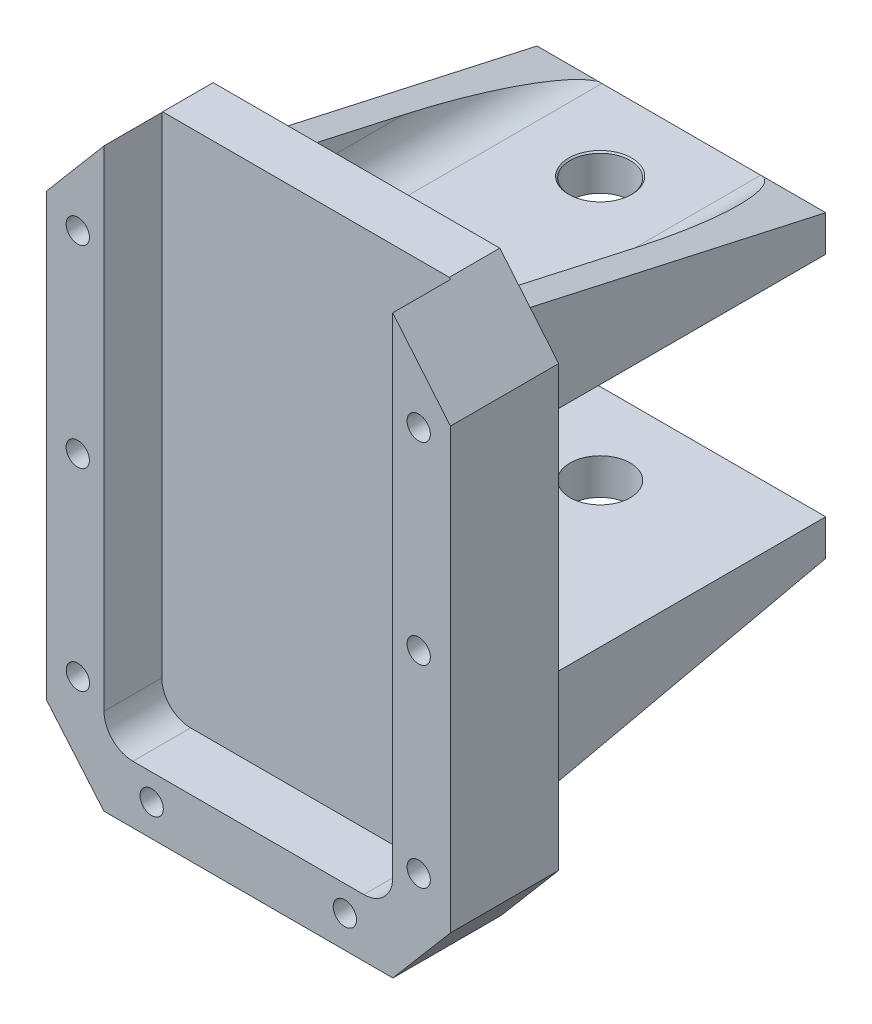
SolidWorks part; units mm, degrees
material "PET"
ref_plane "Front Plane" through (0, 0, 0) normal (0, 0, 1) x (1, 0, 0)
ref_plane "Top Plane" through (0, 0, 0) normal (0, 1, 0) x (1, 0, 0)
ref_plane "Right Plane" through (0, 0, 0) normal (1, 0, 0) x (0, 0, -1)
sketch "Sketch1" plane through (0, 0, 0) normal (0, 0, 1) x (1, 0, 0)
  line L1 (0, 0) -> (-35.56, 0)
  line L2 (0, 0) -> (0, 50.8)
  line L3 (0, 50.8) -> (-35.56, 50.8)
  line L4 (-35.56, 0) -> (-35.56, 50.8)
  dimension "D1" = 50.8
  dimension "D2" = 35.56
extrude "Boss-Extrude1" add sketch "Sketch1" along normal blind 9.525
sketch "Sketch2" plane through (0, 0, 9.525) normal (0, 0, 1) x (1, 0, 0)
  line L0 (0, 50.8) -> (-35.56, 50.8) construction
  line L1 (-30.48, 50.8) -> (-5.08, 50.8)
  line L2 (-30.48, 50.8) -> (-30.48, 5.08)
  line L3 (-30.48, 5.08) -> (-5.08, 5.08)
  line L4 (-5.08, 50.8) -> (-5.08, 5.08)
  line L5 (-35.56, 0) -> (0, 0) construction
  line L6 (-17.78, 0) -> (-17.78, 5.08) construction
  dimension "D1" = 45.72
  dimension "D2" = 25.4
extrude "Cut-Extrude2" cut sketch "Sketch2" against normal blind 5.08
hole_wizard "Tap Drill for M2.5x0.45 Tap1" positions "Sketch6" profile "Sketch5" hole size "M2.5x0.45" standard "ANSI Metric" end condition through all
sketch "Sketch6" plane through (0, 0, 0) normal (0, 0, -1) x (-1, 0, 0)
  point P0 (2.7924, 43.0871)
  point P2 (2.7924, 26.093)
  point P4 (2.7924, 9.1052)
  point P6 (9.2907, 2.8227)
  point P8 (26.2924, 2.7871)
  point P10 (32.78, 9.1052)
  point P12 (32.7924, 26.0871)
  point P14 (32.7924, 43.0871)
sketch "Sketch5" plane through (-2.7924, 43.0871, 0) normal (1, 0, 0) x (0, 1, 0)
  line L0 (0, 0) -> (0, 9.525)
  line L1 (0, 9.525) -> (1.025, 9.525)
  line L2 (1.025, 9.525) -> (1.025, 0)
  line L5 (1.025, 0) -> (0, 0)
  line L11 (0, -6.35) -> (0, 107.95) construction
  dimension "Thru Hole Dia." = 2.05
  dimension "Thru Hole Depth" = 9.525
sketch "Sketch13" plane through (0, 0, 0) normal (0, 0, -1) x (-1, 0, 0)
  line L0 (35.56, 0) -> (0, 0) construction
  line L1 (30.48, 39.265) -> (5.08, 39.265)
  line L2 (30.48, 39.265) -> (30.48, 36.09)
  line L3 (30.48, 36.09) -> (5.08, 36.09)
  line L4 (5.08, 39.265) -> (5.08, 36.09)
  line L5 (30.48, 39.265) -> (5.08, 36.09) construction
  line L6 (30.48, 36.09) -> (5.08, 39.265) construction
  line L7 (30.48, 16.09) -> (5.08, 16.09)
  line L8 (30.48, 16.09) -> (30.48, 12.915)
  line L9 (30.48, 12.915) -> (5.08, 12.915)
  line L10 (5.08, 16.09) -> (5.08, 12.915)
  line L11 (30.48, 16.09) -> (5.08, 12.915) construction
  line L12 (30.48, 12.915) -> (5.08, 16.09) construction
  line L13 (17.78, 16.09) -> (17.78, 36.09) construction
  line L15 (0, 50.8) -> (35.56, 50.8) construction
  point P0 (17.78, 37.6775)
  point P5 (17.78, 14.5025)
  point P12 (17.78, 0)
  point P15 (17.78, 26.09)
  dimension "D1" = 3.175
  dimension "D2" = 3.175
  dimension "D3" = 25.4
  dimension "D4" = 20
  dimension "D5" = 24.71
extrude "Boss-Extrude2" add sketch "Sketch13" along normal blind 28.575
sketch "Sketch8" plane through (0, 0, 9.525) normal (0, 0, 1) x (1, 0, 0)
  line L0 (-5.179, 50.8) -> (0, 44.5915)
  line L1 (-5.08, 50.8) -> (-30.48, 50.8) construction
  line L2 (0, 0) -> (0, 50.8) construction
  line L3 (0.0027, 44.5883) -> (-5.0973, 50.5883) construction
  line L4 (0, 44.5915) -> (0, 50.8)
  line L5 (0, 50.8) -> (-5.179, 50.8)
  line L6 (-35.56, 44.7066) -> (-35.56, 50.8)
  line L7 (-35.56, 50.8) -> (-35.56, 0) construction
  line L8 (-35.56, 50.8) -> (-30.4026, 50.8)
  line L9 (-30.4026, 50.8) -> (-35.56, 44.7066)
  line L10 (-35.56, 5.97) -> (-35.56, 0)
  line L11 (-35.56, 0) -> (-30.4926, 0)
  line L12 (-35.56, 0) -> (0, 0) construction
  line L13 (-30.4926, 0) -> (-35.56, 5.97)
  line L14 (-5.0926, -0.0313) -> (0, 0)
  line L15 (0, 0) -> (0, 5.97)
  line L16 (0, 5.97) -> (-5.0926, -0.0313)
extrude "Cut-Extrude3" cut sketch "Sketch8" against normal through all
ref_plane "Plane6" through (-23.56, 0, 0) normal (-1, 0, 0) x (0, 0, 1)
fillet "Fillet1" radius 2.54 2 edges at (-5.08, 5.08, 6.985) (-30.48, 5.08, 6.985)
sketch "Sketch10" plane through (-43.87, 39.265, 0) normal (0, -1, 0) x (0, 0, -1)
  line L2 (14.2875, 13.39) -> (14.2875, 38.79) construction
  line L3 (0, 38.79) -> (0, 13.39) construction
  line L4 (14.2875, 26.09) -> (0, 26.09) construction
  line L6 (28.575, 13.39) -> (0, 13.39) construction
  line L7 (28.575, 38.79) -> (0, 38.79) construction
  line L8 (14.2875, 26.09) -> (28.575, 26.09) construction
  line L9 (28.575, 38.79) -> (28.575, 13.39) construction
  circle A0 centre (21.4312, 26.09) radius 3.175
  circle A1 centre (7.1438, 26.09) radius 3.175
  point P10 (23.8125, 26.09)
  dimension "D1" = 6.35
hole_wizard "M5 Clearance Hole1" positions "3DSketch1" profile "Sketch11" hole size "M5" standard "ANSI Metric" end condition through all
sketch3d "3DSketch1"
  point P0 (-17.78, 39.265, -7.1438)
  point P3 (-17.78, 39.265, -21.4312)
sketch "Sketch11" plane through (-17.78, 39.265, -7.1438) normal (1, 0, 0) x (0, 0, 1)
  line L0 (0, 0) -> (0, 39.265)
  line L1 (0, 39.265) -> (2.65, 39.265)
  line L2 (2.65, 39.265) -> (2.65, 0.125)
  line L3 (2.65, 0.125) -> (2.775, 0)
  line L5 (2.775, 0) -> (0, 0)
  line L6 (-2.65, 0.125) -> (-2.775, 0) construction
  line L11 (0, -6.35) -> (0, 107.95) construction
  dimension "Thru Hole Dia." = 5.3
  dimension "Thru Hole Depth" = 39.265
  dimension "Near C'Sink Dia." = 5.55
  dimension "Near C'Sink Angle" = 90
sketch "Sketch14" plane through (-30.48, 0, 0) normal (-1, 0, 0) x (0, 0, 1)
  line L0 (-28.575, 12.915) -> (0, 6.565)
  line L1 (0, 44.7066) -> (0, 5.97) construction
  line L2 (-28.575, 12.915) -> (0, 12.915) construction
  point P5 (0, 0)
  dimension "D1" = 6.35
rib "Rib7" sketch "Sketch14" sketch "Sketch14" thickness 2.54 extrusion direction parallel to sketch draft on no parameters "D1"=2.54
sketch "Sketch15" plane through (-5.08, 0, 0) normal (1, 0, 0) x (0, 0, -1)
  line L0 (28.575, 12.915) -> (0, 6.565)
rib "Rib8" sketch "Sketch15" sketch "Sketch15" thickness 2.54 extrusion direction parallel to sketch draft on no parameters "D1"=2.54
sketch "Sketch16" plane through (-30.48, 0, 0) normal (-1, 0, 0) x (0, 0, 1)
  line L0 (-28.575, 39.265) -> (0, 45.615)
  line L1 (0, 44.7066) -> (0, 5.97) construction
  point P5 (0, 0)
  point P8 (0, 0)
  point P11 (0, 0)
  dimension "D1" = 6.35
sketch "Sketch17" plane through (-5.08, 0, 0) normal (1, 0, 0) x (0, 0, -1)
  line L0 (28.575, 39.265) -> (0, 45.615)
rib "Rib9" sketch "Sketch17" sketch "Sketch17" thickness 2.54 extrusion direction parallel to sketch draft on no parameters "D1"=2.54
rib "Rib10" sketch "Sketch16" sketch "Sketch16" thickness 2.54 extrusion direction parallel to sketch draft on no parameters "D1"=2.54
fillet "Fillet2" radius 3.175 2 edges at (-27.94, 12.915, -14.2875) (-7.62, 12.915, -14.2875)
fillet "Fillet3" radius 3.175 2 edges at (-7.62, 39.265, -14.2875) (-27.94, 39.265, -14.2875)
